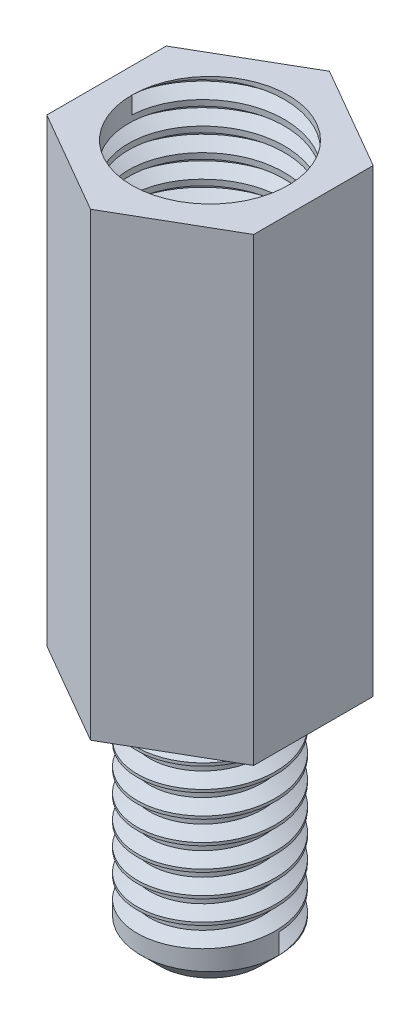
SolidWorks part; units mm, degrees
material "Nylon 101"
ref_plane "Front Plane" through (0, 0, 0) normal (0, 0, 1) x (1, 0, 0)
ref_plane "Top Plane" through (0, 0, 0) normal (0, 1, 0) x (1, 0, 0)
ref_plane "Right Plane" through (0, 0, 0) normal (1, 0, 0) x (0, 0, -1)
sketch "Sketch2" plane through (0, 0, 0) normal (0, 1, 0) x (1, 0, 0)
  line L1 (0, 2.5981) -> (-2.25, 1.299)
  line L2 (-2.25, 1.299) -> (-2.25, -1.299)
  line L3 (-2.25, -1.299) -> (0, -2.5981)
  line L4 (0, -2.5981) -> (2.25, -1.299)
  line L5 (2.25, -1.299) -> (2.25, 1.299)
  line L6 (2.25, 1.299) -> (0, 2.5981)
  circle A0 centre (0, 0) radius 2.25 construction
  dimension "D1" = 4.5
extrude "Boss-Extrude1" add sketch "Sketch2" along normal blind 10
hole_wizard "M3 Clearance Hole1" positions "Sketch3" profile "Sketch4" hole size "M3" standard "ISO"
sketch "Sketch3" plane through (0, 10, 0) normal (0, 1, 0) x (1, 0, 0)
  point P0 (0, 0)
sketch "Sketch4" plane through (0, 10, 0) normal (1, 0, 0) x (0, 0, 1)
  line L0 (0, 0) -> (0, 7.0215)
  line L1 (0, 7.0215) -> (1.7, 6)
  line L2 (1.7, 6) -> (1.7, 0)
  line L5 (1.7, 0) -> (0, 0)
  line L10 (0, 7.0215) -> (-1.7, 6) construction
  line L11 (0, -6.35) -> (0, 107.95) construction
  dimension "Hole Dia." = 3.4
  dimension "Hole Depth" = 6
  dimension "Drill Angle" = 118
thread "Thread1" pitch 0.5 method cut profile "Thread Profile1" start angle 0, offset 0, length 4, pitch 0.5, diameter 3.4
ref_plane "Plane1" through (-1.7, 10, 0) normal (0, 0, 1) x (-1, 0, 0)
sketch "Thread Profile1" plane through (-1.7, 10, 0) normal (0, 0, 1) x (-1, 0, 0)
  line L0 (0, 0) -> (0, 0.5) construction
  line L1 (0, 0) -> (0.2706, 0.1562)
  line L2 (0.2706, 0.1562) -> (0.2706, 0.2187)
  line L3 (0.2706, 0.2187) -> (0, 0.375)
  line L4 (0.2706, 0.1875) -> (0, 0.1875) construction
  line L11 (0, 0) -> (0, 0.375)
  point P2 (0, 0)
  dimension "Pitch" = 0.5
  dimension "Profile_Angle" = 60
  dimension "Profile_Land" = 0.0625
  dimension "Profile_Height" = 0.2706
sketch "Sketch10" plane through (0, 0, 0) normal (0, -1, 0) x (1, 0, 0)
  circle A0 centre (0, 0) radius 1.5
  dimension "D1" = 3
extrude "Boss-Extrude2" add sketch "Sketch10" along normal blind 5
chamfer "Chamfer1" distance 0.4 1 edges at (0, -5, -1.5)
thread "Thread3" pitch 0.5 method cut profile "Thread Profile3" start angle 0, offset 0, length 4.6, pitch 0.5, diameter 3
ref_plane "Plane3" through (1.5, -4.6, 0) normal (0, 0, 1) x (1, 0, 0)
sketch "Thread Profile3" plane through (1.5, -4.6, 0) normal (0, 0, 1) x (1, 0, 0)
  line L0 (0, 0) -> (0, 0.5) construction
  line L11 (0, 0) -> (0, 0.4375)
  line L12 (0, 0.4375) -> (-0.2706, 0.2812)
  line L13 (-0.2706, 0.2812) -> (-0.2706, 0.1562)
  line L15 (-0.2706, 0.1562) -> (0, 0)
  line L17 (-0.2706, 0.2187) -> (0, 0.2187) construction
  point P2 (0, 0)
  dimension "Pitch" = 0.5
  dimension "Profile_Angle" = 60
  dimension "Profile_Land" = 0.125
  dimension "Profile_Height" = 0.2706
